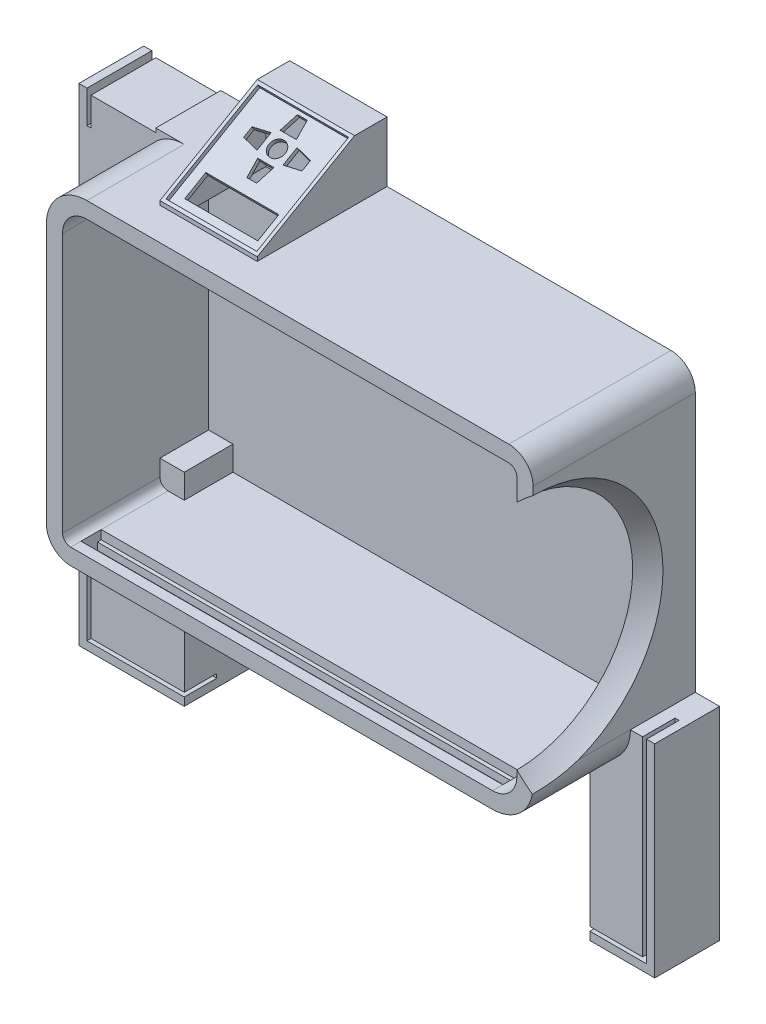
SolidWorks part; units mm, degrees
ref_plane "Front Plane" through (0, 0, 0) normal (0, 0, 1) x (1, 0, 0)
ref_plane "Top Plane" through (0, 0, 0) normal (0, 1, 0) x (1, 0, 0)
ref_plane "Right Plane" through (0, 0, 0) normal (1, 0, 0) x (0, 0, -1)
sketch "Sketch1" plane through (0, 0, 0) normal (0, 0, 1) x (1, 0, 0)
  line L1 (-190.5, -127) -> (190.5, -127)
  line L2 (-190.5, -127) -> (-190.5, 127)
  line L3 (-190.5, 127) -> (190.5, 127)
  line L4 (190.5, -127) -> (190.5, 127)
  line L5 (-190.5, -127) -> (190.5, 127) construction
  line L6 (-190.5, 127) -> (190.5, -127) construction
  point P0 (0, 0)
  dimension "D1" = 381
  dimension "D2" = 254
extrude "Boss-Extrude1" add sketch "Sketch1" against normal blind 127
fillet "Fillet5" radius 19.05 2 edges at (-190.5, -127, -63.5) (190.5, 127, -63.5)
fillet "Fillet4" radius 31.75 2 edges at (190.5, -127, -63.5) (-190.5, 127, -63.5)
sketch "Sketch3" plane through (0, 0, 0) normal (0, 0, -1) x (-1, 0, 0)
  line L16 (-158.75, -114.3) -> (171.45, -114.3)
  line L17 (-177.8, 107.95) -> (-177.8, -95.25)
  line L18 (158.75, 114.3) -> (-171.45, 114.3)
  line L19 (177.8, -107.95) -> (177.8, 95.25)
  line L20 (-158.75, -114.3) -> (171.45, -114.3)
  line L21 (-177.8, 107.95) -> (-177.8, -95.25)
  line L22 (158.75, 114.3) -> (-171.45, 114.3)
  line L23 (177.8, -107.95) -> (177.8, 95.25)
  arc A13 (-177.8, -95.25) -> (-158.75, -114.3) centre (-158.75, -95.25) ccw
  arc A14 (-171.45, 114.3) -> (-177.8, 107.95) centre (-171.45, 107.95) ccw
  arc A15 (177.8, 95.25) -> (158.75, 114.3) centre (158.75, 95.25) ccw
  arc A16 (171.45, -114.3) -> (177.8, -107.95) centre (171.45, -107.95) ccw
  arc A17 (-177.8, -95.25) -> (-158.75, -114.3) centre (-158.75, -95.25) ccw
  arc A18 (-171.45, 114.3) -> (-177.8, 107.95) centre (-171.45, 107.95) ccw
  arc A19 (177.8, 95.25) -> (158.75, 114.3) centre (158.75, 95.25) ccw
  arc A20 (171.45, -114.3) -> (177.8, -107.95) centre (171.45, -107.95) ccw
  dimension "D1" = 12.7
extrude "Cut-Extrude1" cut sketch "Sketch3" along normal offset from surface (114.3 mm away) 12.7 up to face at (0, 0, -127)
sketch "Sketch5" plane through (0, -127, 0) normal (0, -1, 0) x (1, 0, 0)
  line L0 (158.75, -127) -> (158.75, 0) construction
  line L1 (158.75, -10.455) -> (-171.45, -10.455)
  line L2 (158.75, -10.455) -> (158.75, -20.955)
  line L3 (158.75, -20.955) -> (-171.45, -20.955)
  line L4 (-171.45, -10.455) -> (-171.45, -20.955)
  line L5 (-171.45, 0) -> (-171.45, -127) construction
  line L7 (-171.45, 0) -> (158.75, 0) construction
  dimension "D1" = 10.5
  dimension "D2" = 20.955
extrude "Cut-Extrude2" cut sketch "Sketch5" against normal up to next
ref_plane "Plane1" through (0, 0, 0) normal (0, 1, 0) x (1, 0, 0)
sketch "Sketch6" plane through (0, 0, 0) normal (0, 1, 0) x (1, 0, 0)
  line L0 (139.7, 0) -> (266.7, 0)
  line L1 (171.45, 0) -> (-158.75, 0) construction
  line L2 (266.7, 0) -> (266.7, 127)
  line L3 (171.45, 127) -> (-158.75, 127) construction
  line L4 (190.5, 127) -> (190.5, 0) construction
  arc A0 (139.7, 0) -> (266.7, 127) centre (266.7, 0) cw
  dimension "D1" = 76.2
revolve "Cut-Revolve1" cut sketch "Sketch6" angle 360 about L2
sketch "Sketch7" plane through (0, 0, -127) normal (0, 0, -1) x (-1, 0, 0)
  line L0 (190.5, 95.25) -> (190.5, -107.95) construction
  line L1 (158.75, 127) -> (241.3, 127)
  line L2 (158.75, 127) -> (158.75, 50.8)
  line L3 (158.75, 50.8) -> (241.3, 50.8)
  line L4 (241.3, 127) -> (241.3, 50.8)
  line L5 (171.45, -127) -> (-158.75, -127) construction
  line L6 (234.95, 127) -> (231.775, 127)
  line L7 (234.95, 127) -> (234.95, 101.6)
  line L8 (234.95, 101.6) -> (231.775, 101.6)
  line L9 (231.775, 127) -> (231.775, 101.6)
  line L10 (-158.75, -95.25) -> (-209.55, -95.25)
  line L11 (-158.75, -95.25) -> (-158.75, -254)
  line L12 (-158.75, -254) -> (-209.55, -254)
  line L13 (-209.55, -95.25) -> (-209.55, -254)
  line L14 (0, 127) -> (0, -127) construction
  line L15 (-171.45, 127) -> (158.75, 127) construction
  line L16 (158.75, -254) -> (241.3, -254)
  line L17 (241.3, -95.25) -> (241.3, -254)
  line L18 (158.75, -95.25) -> (241.3, -95.25)
  line L19 (158.75, -95.25) -> (158.75, -254)
  line L21 (231.775, 127) -> (180.975, 127)
  line L22 (231.775, 127) -> (231.775, 123.825)
  line L23 (231.775, 123.825) -> (180.975, 123.825)
  line L24 (180.975, 127) -> (180.975, 123.825)
  line M11 (190.5, -107.95) -> (190.5, 95.25)
  arc M12 (190.5, 95.25) -> (158.75, 127) centre (158.75, 95.25) ccw
  dimension "D1" = 50.8
  dimension "D2" = 76.2
  dimension "D3" = 3.175
  dimension "D4" = 6.35
  dimension "D5" = 25.4
  dimension "D6" = 50.8
  dimension "D7" = 127
  dimension "D8" = 50.8
extrude "Boss-Extrude2" add sketch "Sketch7" against normal blind 50.8 contours L9 L1 L3 L4 L7 L8 M12 M11 | L16 L17 L18 L19 | L11 L10 L13 L12 region at (-214.1054, 88.5803, -127)
sketch "Sketch8" plane through (0, 0, -76.2) normal (0, 0, 1) x (1, 0, 0)
  line L0 (-234.95, -95.25) -> (-234.95, -247.65)
  line L1 (-190.5, -95.25) -> (-241.3, -95.25) construction
  line L2 (-234.95, -247.65) -> (-158.75, -247.65)
  line L3 (-158.75, -127) -> (-158.75, -254) construction
  line L4 (-158.75, -247.65) -> (-158.75, -244.475)
  line L5 (-158.75, -244.475) -> (-231.775, -244.475)
  line L6 (-231.775, -244.475) -> (-231.775, -95.25)
  line L7 (-231.775, -95.25) -> (-234.95, -95.25)
  line L8 (-234.95, 101.6) -> (-231.775, 101.6) construction
  line L9 (-234.95, 127) -> (-234.95, 101.6) construction
  line L10 (-158.75, -254) -> (-241.3, -254) construction
  line L11 (158.75, -247.65) -> (203.2, -247.65)
  line L12 (158.75, -127) -> (158.75, -254) construction
  line L13 (203.2, -247.65) -> (203.2, -95.25)
  line L14 (190.5, -95.25) -> (209.55, -95.25) construction
  line L15 (203.2, -95.25) -> (200.025, -95.25)
  line L16 (200.025, -95.25) -> (200.025, -244.475)
  line L17 (200.025, -244.475) -> (158.75, -244.475)
  line L18 (158.75, -244.475) -> (158.75, -247.65)
  line L19 (209.55, -95.25) -> (209.55, -254) construction
  dimension "D1" = 6.35
  dimension "D2" = 6.35
extrude "Cut-Extrude3" cut sketch "Sketch8" against normal blind 25.4
ref_plane "Plane2" through (-127, 0, 0) normal (1, 0, 0) x (0, 0, -1)
sketch "Sketch9" plane through (-127, 0, 0) normal (1, 0, 0) x (0, 0, -1)
  line L0 (25.4, 127) -> (25.4, 130.175)
  line L1 (0, 127) -> (127, 127) construction
  line L2 (25.4, 130.175) -> (101.6, 174.1691)
  line L4 (25.4, 127) -> (127, 127)
  line L5 (0, 127) -> (0, 107.95) construction
  line L6 (101.6, 174.1691) -> (127, 174.1691)
  line L7 (127, 174.1691) -> (127, 127)
  line L8 (127, 107.95) -> (127, 127) construction
  dimension "D1" = 25.4
  dimension "D3" = 25.4
  dimension "D4" = 3.175
  dimension "D5" = 60
extrude "Boss-Extrude3" add sketch "Sketch9" along normal blind 76.2
sketch "Sketch10" plane through (0, 86.6327, 50.0174) normal (0, 0.866, 0.5) x (1, 0, 0)
  line L8 (-124.46, 172.5327) -> (-124.46, 89.6245)
  line L9 (-124.46, 89.6245) -> (-53.34, 89.6245)
  line L10 (-53.34, 89.6245) -> (-53.34, 172.5327)
  line L11 (-53.34, 172.5327) -> (-124.46, 172.5327)
  line L12 (-124.46, 172.5327) -> (-124.46, 89.6245)
  line L13 (-124.46, 89.6245) -> (-53.34, 89.6245)
  line L14 (-53.34, 89.6245) -> (-53.34, 172.5327)
  line L15 (-53.34, 172.5327) -> (-124.46, 172.5327)
  dimension "D1" = 2.54
extrude "Cut-Extrude4" cut sketch "Sketch10" against normal blind 12.7
sketch "Sketch11" plane through (0, 114.3, 0) normal (0, -1, 0) x (1, 0, 0)
  line L0 (-124.46, -33.9497) -> (-53.34, -33.9497) construction
  line L1 (-124.46, -33.9497) -> (-53.34, -33.9497)
  line L2 (-124.46, -33.9497) -> (-124.46, -105.7503)
  line L3 (-124.46, -105.7503) -> (-53.34, -105.7503)
  line L4 (-53.34, -33.9497) -> (-53.34, -105.7503)
  line L5 (-124.46, -105.7503) -> (-124.46, -33.9497) construction
  line L6 (-53.34, -105.7503) -> (-124.46, -105.7503) construction
  line L7 (-53.34, -33.9497) -> (-53.34, -105.7503) construction
extrude "Cut-Extrude5" cut sketch "Sketch11" against normal up to surface (6.1465 mm away) up to face at (-88.9, 141.1735, -69.85)
ref_plane "Plane3" through (0, 83.8831, 48.4299) normal (0, 0.866, 0.5) x (1, 0, 0)
sketch "Sketch12" plane through (0, 83.8831, 48.4299) normal (0, 0.866, 0.5) x (1, 0, 0)
  line L0 (-53.34, 89.6245) -> (-53.34, 172.5327) construction
  line L1 (-124.46, 89.6245) -> (-53.34, 89.6245) construction
  line L2 (-124.46, 172.5327) -> (-124.46, 89.6245) construction
  line L3 (-53.34, 172.5327) -> (-124.46, 172.5327) construction
  line L4 (-53.34, 89.6245) -> (-53.34, 172.5327)
  line L5 (-124.46, 89.6245) -> (-53.34, 89.6245)
  line L6 (-124.46, 172.5327) -> (-124.46, 89.6245)
  line L7 (-53.34, 172.5327) -> (-124.46, 172.5327)
  line L8 (-88.9, 172.5327) -> (-88.9, 89.6245) construction
  line L9 (-82.55, 136.9727) -> (-95.25, 136.9727)
  line L10 (-78.74, 153.4827) -> (-66.04, 150.9427)
  line L11 (-78.74, 153.4827) -> (-78.74, 140.7827)
  line L12 (-78.74, 140.7827) -> (-66.04, 143.3227)
  line L13 (-66.04, 150.9427) -> (-66.04, 143.3227)
  line L14 (-82.55, 136.9727) -> (-85.09, 124.2727)
  line L15 (-85.09, 124.2727) -> (-92.71, 124.2727)
  line L16 (-95.25, 136.9727) -> (-92.71, 124.2727)
  line L17 (-99.06, 140.7827) -> (-99.06, 153.4827)
  line L18 (-99.06, 140.7827) -> (-111.76, 143.3227)
  line L19 (-111.76, 143.3227) -> (-111.76, 150.9427)
  line L20 (-99.06, 153.4827) -> (-111.76, 150.9427)
  line L21 (-95.25, 157.2927) -> (-82.55, 157.2927)
  line L22 (-95.25, 157.2927) -> (-92.71, 169.9927)
  line L23 (-92.71, 169.9927) -> (-85.09, 169.9927)
  line L24 (-82.55, 157.2927) -> (-85.09, 169.9927)
  line L26 (-116.84, 95.9745) -> (-59.69, 95.9745)
  line L27 (-116.84, 95.9745) -> (-116.84, 115.0245)
  line L28 (-116.84, 115.0245) -> (-59.69, 115.0245)
  line L29 (-59.69, 95.9745) -> (-59.69, 115.0245)
  circle A0 centre (-88.9, 147.1327) radius 6.35
  point P20 (-88.9, 153.4827)
  dimension "D1" = 12.7
  dimension "D2" = 12.7
  dimension "D3" = 10.16
  dimension "D4" = 7.62
  dimension "D5" = 12.7
  dimension "D6" = 25.4
  dimension "D8" = 57.15
  dimension "D9" = 19.05
  dimension "D10" = 6.35
  dimension "D11" = 6.35
  dimension "D7" = 4
extrude "Boss-Extrude4" add sketch "Sketch12" against normal blind 3.175
sketch "Sketch13" plane through (0, -114.3, 0) normal (0, 1, 0) x (1, 0, 0)
  line L8 (-6.35, 20.955) -> (-6.35, 10.455) construction
  line L10 (-171.45, 20.955) -> (158.75, 20.955) construction
  line L12 (158.75, 10.455) -> (-171.45, 10.455) construction
  line L13 (-171.45, 15.955) -> (158.75, 15.955) construction
  line L16 (158.75, 76.2) -> (158.75, 20.955) construction
  line L17 (-171.45, 8.0175) -> (158.75, 8.0175)
  line L18 (-171.45, 8.0175) -> (-171.45, 23.8925)
  line L19 (-171.45, 23.8925) -> (158.75, 23.8925)
  line L20 (158.75, 8.0175) -> (158.75, 23.8925)
  line L21 (-171.45, 15.705) -> (158.75, 15.705) construction
  line L22 (-171.45, 10.455) -> (-171.45, 20.955) construction
  line L23 (158.75, 20.955) -> (158.75, 10.455) construction
  dimension "D1" = 15.875
  dimension "D2" = 0.25
extrude "Cut-Extrude6" cut sketch "Sketch13" against normal blind 7
